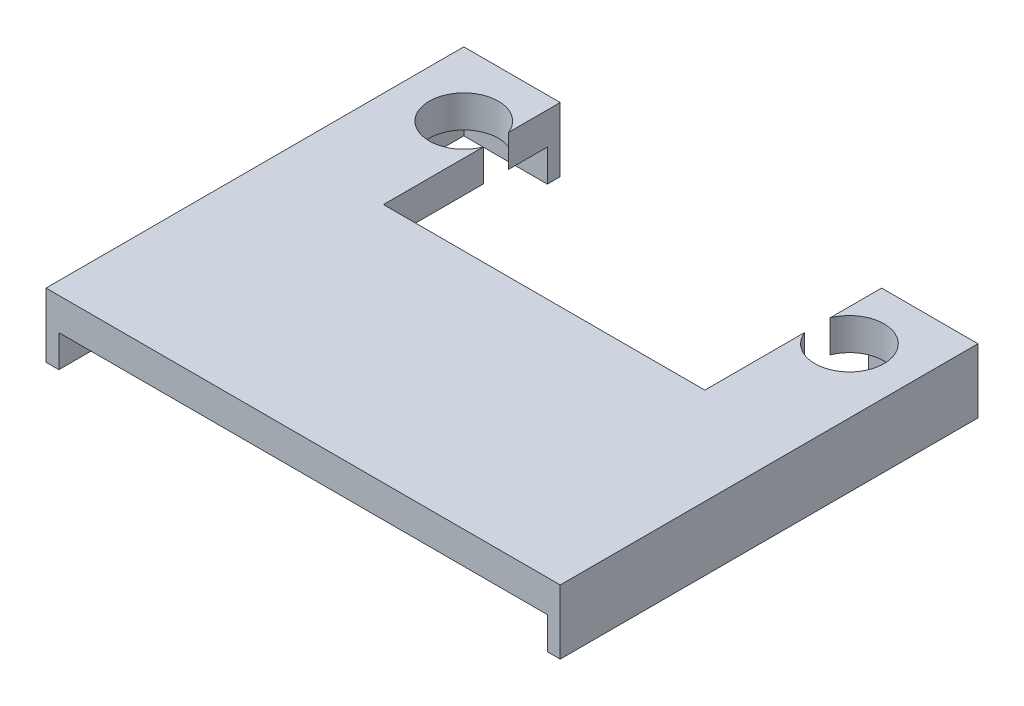
SolidWorks part; units mm, degrees
ref_plane "Front Plane" through (0, 0, 0) normal (0, 0, 1) x (1, 0, 0)
ref_plane "Top Plane" through (0, 0, 0) normal (0, 1, 0) x (1, 0, 0)
ref_plane "Right Plane" through (0, 0, 0) normal (1, 0, 0) x (0, 0, -1)
sketch "Sketch1" plane through (0, 0, 0) normal (0, 1, 0) x (1, 0, 0)
  line L0 (0, 40) -> (0, -40) construction
  line L1 (-40, -40) -> (40, -40)
  line L2 (-40, -40) -> (-40, 40)
  line L3 (-40, 40) -> (40, 40)
  line L4 (40, -40) -> (40, 40)
  line L5 (-40, -40) -> (40, 40) construction
  line L6 (-40, 40) -> (40, -40) construction
  line L7 (0, 0) -> (-30, 0) construction
  line L8 (-30, -40) -> (-30, 30) construction
  line L9 (-24.6254, 30) -> (24.6254, 30) construction
  line L10 (-23, 22) -> (-23, 38)
  line L11 (-25, 20) -> (25, 20)
  line L12 (-25, 20) -> (-25, 40)
  line L13 (-25, 40) -> (25, 40)
  line L14 (25, 20) -> (25, 40)
  line L15 (-25, 20) -> (25, 40) construction
  line L16 (-25, 40) -> (25, 20) construction
  line L18 (23, 22) -> (23, 38)
  line L20 (-23, 38) -> (23, 38) construction
  line L21 (-23, 22) -> (23, 22) construction
  line L22 (30, 30) -> (40, 30) construction
  line L23 (-25, 20) -> (25, 20)
  line L24 (-25, 20) -> (-25, 12.5)
  line L25 (25, 20) -> (25, 12.5)
  line L26 (-25, 12.5) -> (25, 12.5)
  line L27 (-10.2957, 20) -> (-10.2957, 12.5) construction
  circle A0 centre (-30, 30) radius 5.3746
  circle A1 centre (30, 30) radius 5.3746
  point P0 (0, 0)
  point P17 (0, 30)
  dimension "D1" = 2
extrude "Boss-Extrude2" add sketch "Sketch1" along normal blind 10 contours L2 L3 L4 L1
extrude "Cut-Extrude2" cut sketch "Sketch1<8>" along normal blind 14 contours L24 L26 L25 L11 | A1 | L11 L14 L13 L12 | A0 region at (0, 0, -16.25)
sketch "Sketch1<8>" plane through (0, 0, 0) normal (0, 1, 0) x (1, 0, 0) same geometry as "Sketch1"
sketch "Sketch4" plane through (0, 0, 0) normal (0, -1, 0) x (1, 0, 0)
  line L0 (40, 40) -> (40, -40) construction
  line L1 (-40, 40) -> (40, 40)
  line L2 (-40, 40) -> (-40, 25)
  line L3 (-40, 25) -> (40, 25)
  line L4 (40, 40) -> (40, 25)
  line L5 (0, 25) -> (0, 40) construction
  line L6 (-27, -38) -> (27, -38)
  line L7 (-40, 25) -> (-40, -40)
  line L8 (-40, -40) -> (-25, -40)
  line L9 (-25, -40) -> (-25, -12.5)
  line L10 (-25, -12.5) -> (25, -12.5)
  line L11 (25, -12.5) -> (25, -40)
  line L12 (25, -40) -> (40, -40)
  line L13 (40, -40) -> (40, 25)
  line L14 (-38, 25) -> (-38, -38)
  line L15 (-38, -38) -> (-27, -38)
  line L19 (27, -38) -> (38, -38)
  line L20 (38, -38) -> (38, 25)
  line L21 (-27, -10.5) -> (27, -10.5) construction
  line L22 (27, -10.5) -> (27, -38) construction
  line L23 (-27, -38) -> (-27, -10.5) construction
  arc M6 (-25, -31.9715) -> (-25, -28.0285) centre (-30, -30) cw
  arc M10 (25, -28.0285) -> (25, -31.9715) centre (30, -30) cw
  line M13 (40, -40) -> (40, 40)
  line M14 (40, 40) -> (-40, 40)
  line M15 (-40, 40) -> (-40, -40)
  dimension "D1" = 2
extrude "Cut-Extrude3" cut sketch "Sketch4" against normal blind 14 contours L3 M15 M13 M14 region at (0, 0, 32.5)
extrude "Cut-Extrude4" cut sketch "Sketch4<4>" against normal blind 5 contours L19 L20 L3 L14 L15 M6 M10 region at (0, 0, 1.9371)
sketch "Sketch4<4>" plane through (0, 0, 0) normal (0, -1, 0) x (1, 0, 0) same geometry as "Sketch4"
scale "Scale2" scale about centroid uniform scaling yes scale factor 0.1
